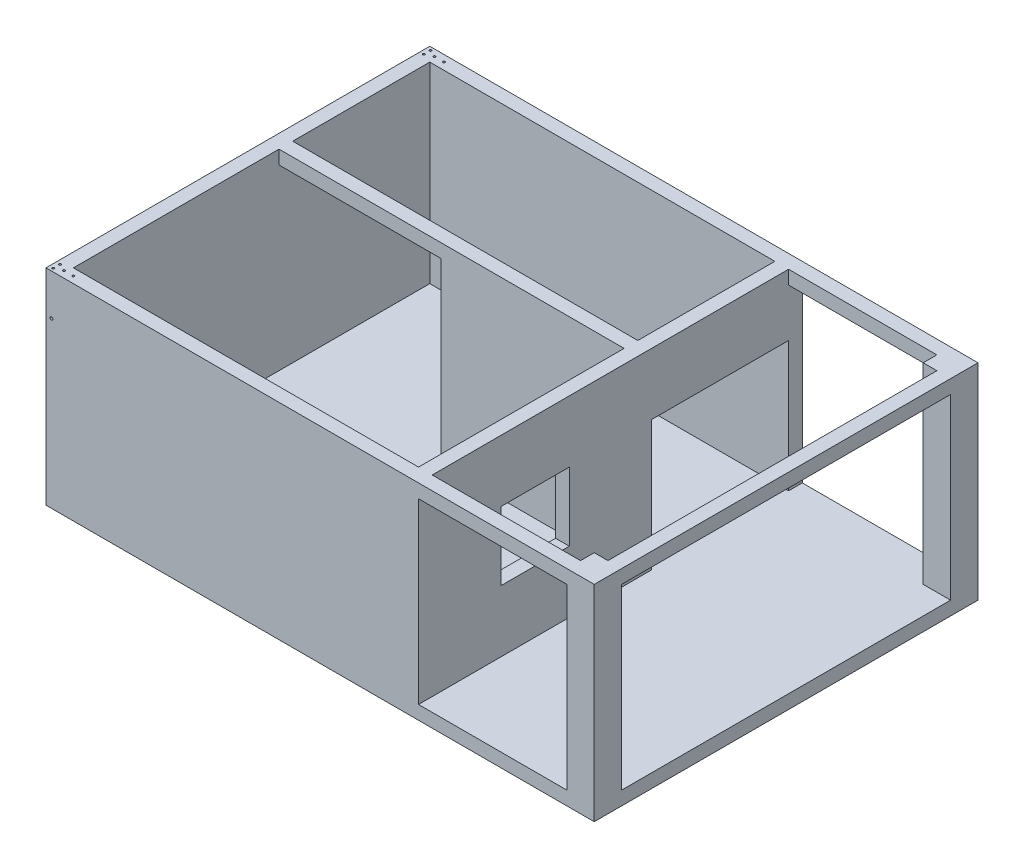
SolidWorks part; units mm, degrees
material "Pine"
ref_plane "Front Plane" through (0, 0, 0) normal (0, 0, 1) x (1, 0, 0)
ref_plane "Top Plane" through (0, 0, 0) normal (0, 1, 0) x (1, 0, 0)
ref_plane "Right Plane" through (0, 0, 0) normal (1, 0, 0) x (0, 0, -1)
sketch "Sketch1" plane through (0, 0, 0) normal (0, 1, 0) x (1, 0, 0)
  line L1 (0, 0) -> (2000, 0)
  line L2 (0, 0) -> (0, 1400)
  line L3 (0, 1400) -> (2000, 1400)
  line L4 (2000, 0) -> (2000, 1400)
  dimension "D1" = 2000
  dimension "D2" = 1400
extrude "Boss-Extrude1" add sketch "Sketch1" along normal blind 50
sketch "Sketch2" plane through (0, 50, 0) normal (0, 1, 0) x (1, 0, 0)
  line L0 (0, 700) -> (2000, 700) construction
  line L1 (2000, 1400) -> (1900, 1400)
  line L2 (2000, 1400) -> (2000, 1300)
  line L3 (2000, 1300) -> (1900, 1300)
  line L4 (1900, 1400) -> (1900, 1300)
  line L5 (0, 1400) -> (0, 0) construction
  line L6 (2000, 0) -> (2000, 1400) construction
  line L7 (2000, 100) -> (1900, 100)
  line L8 (1900, 0) -> (1900, 100)
  line L9 (2000, 0) -> (1900, 0)
  line L10 (2000, 0) -> (2000, 100)
  line L11 (0, 1350) -> (1359, 1350)
  line L12 (0, 0) -> (1359, 0)
  line L13 (0, 0) -> (0, 50)
  line L14 (0, 50) -> (1359, 50)
  line L15 (1359, 0) -> (1359, 50)
  line L16 (1359, 1400) -> (1359, 1350)
  line L17 (0, 1400) -> (1359, 1400)
  line L18 (0, 1400) -> (0, 1350)
  line L20 (0, 1350) -> (50, 1350)
  line L21 (0, 1350) -> (0, 50)
  line L22 (0, 50) -> (50, 50)
  line L23 (50, 1350) -> (50, 50)
  line L24 (641, 850) -> (1359, 850)
  line L25 (641, 850) -> (641, 800)
  line L26 (641, 800) -> (1359, 800)
  line L27 (1359, 850) -> (1359, 800)
  dimension "D1" = 100
  dimension "D2" = 100
  dimension "D3" = 1359
  dimension "D4" = 50
  dimension "D5" = 50
  dimension "D6" = 718
  dimension "D7" = 50
  dimension "D8" = 591
  dimension "D9" = 500
extrude "Boss-Extrude2" add sketch "Sketch2" along normal blind 700 contours L11 L16 L17 L18 | L21 L20 L23 L22 | L13 L12 L15 L14 | L25 L24 L27 L26 | L2 L1 L4 L3 | L7 L8 L9 L10
sketch "Sketch3" plane through (641, 0, 0) normal (-1, 0, 0) x (0, 0, 1)
  line L0 (-800, 750) -> (-800, 50) construction
  line L1 (-850, 750) -> (-800, 750)
  line L2 (-850, 750) -> (-850, 700)
  line L3 (-850, 700) -> (-800, 700)
  line L4 (-800, 750) -> (-800, 700)
  dimension "D1" = 50
extrude "Boss-Extrude3" add sketch "Sketch3" along normal up to surface (591 mm away) up to face at (50, 400, -700)
sketch "Sketch4" plane through (0, 50, 0) normal (0, 1, 0) x (1, 0, 0)
  line L0 (50, 50) -> (1359, 50) construction
  line L1 (1359, 800) -> (1309, 800)
  line L2 (1359, 800) -> (1359, 50)
  line L3 (1359, 50) -> (1309, 50)
  line L4 (1309, 800) -> (1309, 50)
  dimension "D1" = 50
extrude "Boss-Extrude4" add sketch "Sketch4" along normal up to vertex (700 mm away) up to point (1359, 750, -50)
sketch "Sketch5" plane through (1359, 0, 0) normal (1, 0, 0) x (0, 0, -1)
  line L1 (300, 525) -> (550, 525)
  line L2 (300, 525) -> (300, 275)
  line L3 (300, 275) -> (550, 275)
  line L4 (550, 525) -> (550, 275)
  line L5 (850, 750) -> (0, 750) construction
  line L6 (850, 750) -> (850, 50) construction
  dimension "D1" = 250
  dimension "D2" = 250
  dimension "D3" = 225
  dimension "D4" = 300
extrude "Cut-Extrude1" cut sketch "Sketch5" against normal blind 700
sketch "Sketch6" plane through (0, 0, -1350) normal (0, 0, 1) x (1, 0, 0)
  line L1 (1359, 750) -> (1309, 750)
  line L2 (1359, 750) -> (1359, 525)
  line L3 (1359, 525) -> (1309, 525)
  line L4 (1309, 750) -> (1309, 525)
  dimension "D1" = 225
  dimension "D2" = 50
extrude "Boss-Extrude5" add sketch "Sketch6" along normal up to surface (500 mm away) up to face at (683.3333, 500, -850)
sketch "Sketch7" plane through (0, 525, 0) normal (0, -1, 0) x (1, 0, 0)
sketch "Sketch8" plane through (1359, 0, 0) normal (1, 0, 0) x (0, 0, -1)
  line L0 (700, 750) -> (700, 0) construction
  line L1 (0, 750) -> (50, 750)
  line L2 (0, 750) -> (0, 700)
  line L3 (0, 700) -> (50, 700)
  line L4 (50, 750) -> (50, 700)
  line L5 (1400, 750) -> (0, 750) construction
  line L6 (0, 0) -> (1400, 0) construction
  line L7 (1400, 700) -> (1350, 700)
  line L8 (1350, 750) -> (1350, 700)
  line L9 (1400, 750) -> (1350, 750)
  line L10 (1400, 750) -> (1400, 700)
  dimension "D1" = 50
  dimension "D2" = 50
extrude "Boss-Extrude6" add sketch "Sketch8" along direction (-1, 0, 0) on the side of the normal up to surface (541 mm away) contours L2 L1 L4 L3 | L7 L8 L9 L10 up to face at (1900, 400, -50)
sketch "Sketch9" plane through (0, 0, -1300) normal (0, 0, 1) x (1, 0, 0)
  line L1 (2000, 750) -> (1950, 750)
  line L2 (2000, 750) -> (2000, 700)
  line L3 (2000, 700) -> (1950, 700)
  line L4 (1950, 750) -> (1950, 700)
  dimension "D1" = 50
  dimension "D2" = 50
extrude "Boss-Extrude7" add sketch "Sketch9" along normal up to surface (1200 mm away) up to face at (1950, 400, -100)
sketch "Sketch11" plane through (0, 0, 0) normal (0, 0, 1) x (1, 0, 0)
  line L0 (2000, 750) -> (0, 750) construction
  line L1 (0, 750) -> (0, 0) construction
  circle A0 centre (20, 600) radius 5
  dimension "D1" = 10
  dimension "D2" = 150
  dimension "D3" = 20
extrude "Cut-Extrude3" cut sketch "Sketch11" against normal through all both and the other way through all
sketch "Sketch10" plane through (0, 750, 0) normal (0, 1, 0) x (1, 0, 0)
  line L27 (0.007, 1400.0023) -> (135.624, 1389.3162)
  line L29 (-0.0259, 35.8312) -> (135.5911, 25.1452)
  line L30 (-0.0117, 26.8312) -> (-0.0259, 35.8312)
  line L31 (135.606, 15.7452) -> (135.6132, 11.1452)
  line L32 (135.6132, 11.1452) -> (0.0306, 0.0313)
  line L33 (0.0306, 0.0313) -> (0.0164, 9.0312)
  line L34 (0.0164, 9.0312) -> (-8.4836, 9.0178)
  line L35 (-8.4836, 9.0178) -> (-8.5117, 26.8178)
  line L45 (-8.5117, 26.8178) -> (-0.0117, 26.8312)
  line L46 (135.5911, 25.1452) -> (135.5984, 20.5452)
  line L47 (135.6132, 11.1452) -> (0.0306, 0.0313)
  line L48 (135.606, 15.7452) -> (135.6132, 11.1452)
  line L49 (135.5911, 25.1452) -> (135.5984, 20.5452)
  line L50 (-8.5117, 26.8178) -> (-0.0117, 26.8312)
  line L51 (-8.4836, 9.0178) -> (-8.5117, 26.8178)
  line L52 (0.0164, 9.0312) -> (-8.4836, 9.0178)
  line L53 (0.0306, 0.0313) -> (0.0164, 9.0312)
  line L54 (0.0212, 1391.0023) -> (0.007, 1400.0023)
  line L55 (135.6388, 1379.9162) -> (135.6461, 1375.3162)
  line L56 (135.6461, 1375.3162) -> (0.0635, 1364.2023)
  line L57 (0.0635, 1364.2023) -> (0.0493, 1373.2023)
  line L58 (0.0493, 1373.2023) -> (-8.4507, 1373.1889)
  line L59 (-8.4507, 1373.1889) -> (-8.4788, 1390.9889)
  line L60 (-8.4788, 1390.9889) -> (0.0212, 1391.0023)
  line L61 (135.624, 1389.3162) -> (135.6313, 1384.7162)
  line L62 (135.6461, 1375.3162) -> (0.0635, 1364.2023)
  line L63 (135.6388, 1379.9162) -> (135.6461, 1375.3162)
  line L64 (135.624, 1389.3162) -> (135.6313, 1384.7162)
  line L65 (-8.4788, 1390.9889) -> (0.0212, 1391.0023)
  line L66 (-8.4507, 1373.1889) -> (-8.4788, 1390.9889)
  line L67 (0.0493, 1373.2023) -> (-8.4507, 1373.1889)
  line L68 (0.0635, 1364.2023) -> (0.0493, 1373.2023)
  arc A11 (135.5984, 20.5452) -> (135.606, 15.7452) centre (135.6022, 18.1452) cw
  circle A13 centre (14.6164, 9.0543) radius 2.764
  circle A14 centre (120.6022, 18.1215) radius 2.4
  circle A15 centre (72.6023, 18.0458) radius 2.4
  circle A16 centre (24.5883, 26.87) radius 2.515
  arc A17 (135.5984, 20.5452) -> (135.606, 15.7452) centre (135.6022, 18.1452) cw
  arc A18 (135.6313, 1384.7162) -> (135.6388, 1379.9162) centre (135.635, 1382.3162) cw
  circle A19 centre (14.6492, 1373.2253) radius 2.764
  circle A20 centre (120.6351, 1382.2926) radius 2.4
  circle A21 centre (72.6351, 1382.2168) radius 2.4
  circle A22 centre (24.6211, 1391.0411) radius 2.515
  arc A23 (135.6313, 1384.7162) -> (135.6388, 1379.9162) centre (135.635, 1382.3162) cw
extrude "Cut-Extrude2" [suppressed] cut sketch "Sketch10" against normal blind 10 contours A13 | A16 | A15 | A14 | A19 | A22 | A21 | A20
sketch "Sketch12" plane through (0, 750, 0) normal (0, 1, 0) x (1, 0, 0)
  line L1 (-5, 1396) -> (-5, 1356)
  line L2 (0, 0) -> (0, 1400) construction
  line L3 (-5, 1376) -> (14.5, 1376) construction
  line L4 (14.5, 1388) -> (14.5, 1364) construction
  line L5 (14.5, 1376) -> (41.5, 1376) construction
  line L6 (41.5, 1376) -> (75.5, 1376) construction
  line L7 (-5, 44) -> (-5, 4)
  line L8 (-5, 24) -> (14.5, 24) construction
  line L9 (14.5, 36) -> (14.5, 12) construction
  line L10 (14.5, 24) -> (41.5, 24) construction
  line L11 (41.5, 24) -> (75.5, 24) construction
  circle A4 centre (14.5, 36) radius 4
  circle A5 centre (14.5, 12) radius 4
  circle A6 centre (41.5, 24) radius 4
  circle A7 centre (75.5, 24) radius 4
  circle A8 centre (14.5, 1388) radius 4
  circle A9 centre (14.5, 1364) radius 4
  circle A10 centre (41.5, 1376) radius 4
  circle A11 centre (75.5, 1376) radius 4
  point P9 (14.5, 1376)
  point P24 (14.5, 24)
  point P31 (0, 0)
  point P32 (-79.2512, 1474.9449)
  dimension "D5" = 27
  dimension "D10" = 8
  dimension "D4" = 8
  dimension "D2" = 19.5
  dimension "D3" = 24
  dimension "D6" = 34
  dimension "D7" = 40
  dimension "D8" = 19.5
  dimension "D9" = 24
  dimension "D11" = 27
  dimension "D12" = 34
  dimension "D13" = 5
  dimension "D14" = 4
  dimension "D15" = 40
  dimension "D16" = 5
  dimension "D17" = 4
extrude "Cut-Extrude4" cut sketch "Sketch12" against normal blind 10 and the other way through all contours A11 | A4 | A5 | A6 | A7 | A10 | A9 | A8 region at (14.5, 750, -36) region at (14.5, 750, -12) region at (41.5, 750, -24) region at (75.5, 750, -24) region at (14.5, 750, -1388) region at (14.5, 750, -1364) region at (41.5, 750, -1376) region at (75.5, 750, -1376)
